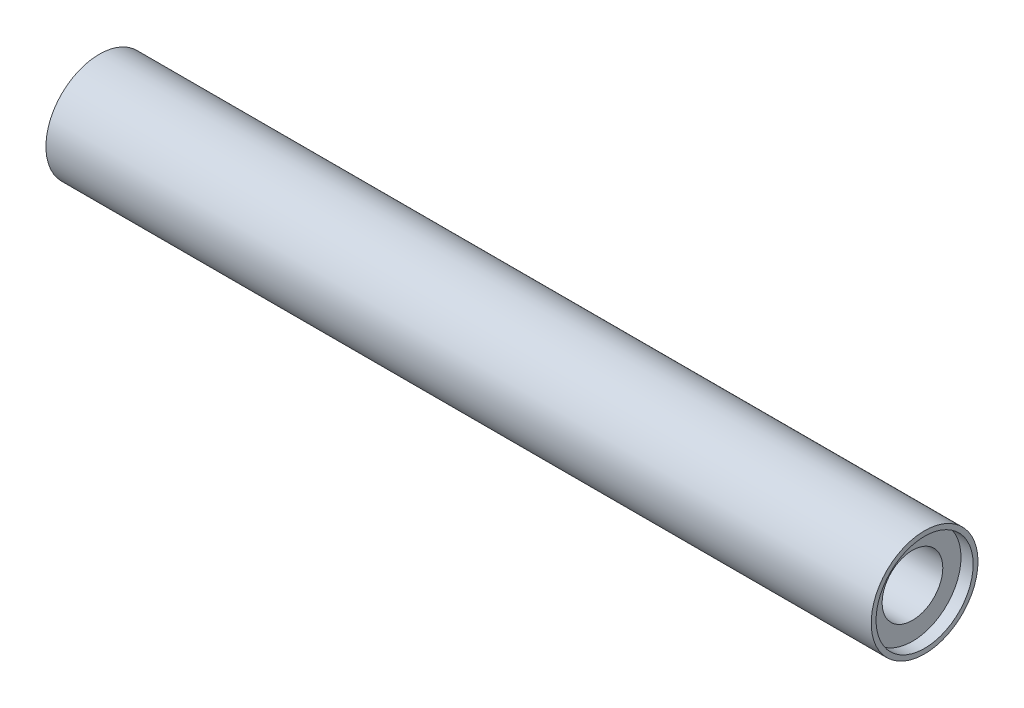
SolidWorks part; units mm, degrees
ref_plane "Front Plane" through (0, 0, 0) normal (0, 0, 1) x (1, 0, 0)
ref_plane "Top Plane" through (0, 0, 0) normal (0, 1, 0) x (1, 0, 0)
ref_plane "Right Plane" through (0, 0, 0) normal (1, 0, 0) x (0, 0, -1)
sketch "Sketch1" plane through (0, 0, 0) normal (1, 0, 0) x (0, 0, -1)
  circle A0 centre (0, 0) radius 22
  circle A1 centre (0, 0) radius 12.5
  dimension "D1" = 44
  dimension "D2" = 25
extrude "Boss-Extrude1" add sketch "Sketch1" along normal blind 340
sketch "Sketch2" plane through (0, 0, 0) normal (-1, 0, 0) x (0, 0, 1)
  circle A0 centre (0, 0) radius 20
  dimension "D1" = 40
extrude "Cut-Extrude1" cut sketch "Sketch2" against normal blind 5
extrude "Cut-Extrude2" cut sketch "Sketch2<2>" along normal blind 5 from surface starting at face at (340, 0, -22)
sketch "Sketch2<2>" plane through (0, 0, 0) normal (-1, 0, 0) x (0, 0, 1) same geometry as "Sketch2"
